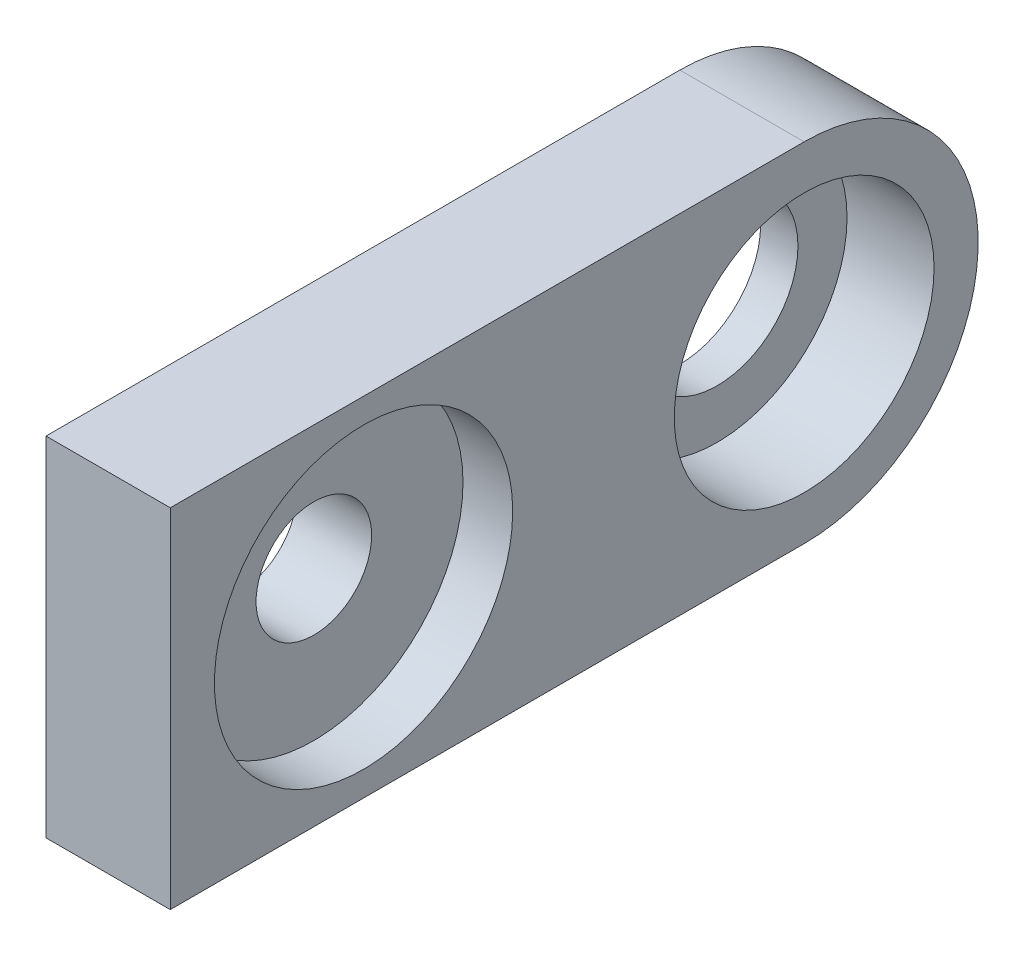
SolidWorks part; units mm, degrees
ref_plane "Front Plane" through (0, 0, 0) normal (1, 0, 0) x (0, 1, 0)
ref_plane "Top Plane" through (0, 0, 0) normal (0, 0, 1) x (0, 1, 0)
ref_plane "Right Plane" through (0, 0, 0) normal (0, 1, 0) x (-1, 0, 0)
sketch "Sketch1" plane through (0, 0, 0) normal (1, 0, 0) x (0, 1, 0)
  line L0 (-14, 0) -> (-14, 51)
  line L1 (14, 0) -> (14, 51)
  line L2 (-14, 51) -> (14, 51)
  line L3 (-14, 51) -> (14, 51) construction
  line L4 (0, 51) -> (0, -14) construction
  line L5 (-14, 0) -> (14, 0) construction
  arc A2 (-14, 0) -> (14, 0) centre (0, 0) ccw
  point P11 (0, 15.0056)
  dimension "D1" = 28
  dimension "D2" = 65
extrude "Boss-Extrude1" add sketch "Sketch1" along normal blind 10
sketch "Sketch2" plane through (10, 0, 0) normal (1, 0, 0) x (0, 1, 0)
  circle A0 centre (0, 0) radius 10.45
  dimension "D1" = 20.9
extrude "Cut-Extrude1" cut sketch "Sketch2" against normal blind 7
sketch "Sketch3" plane through (3, 0, 0) normal (1, 0, 0) x (0, 1, 0)
  circle A0 centre (0, 0) radius 6.5
  dimension "D1" = 13
extrude "Cut-Extrude2" cut sketch "Sketch3" against normal through all
sketch "Sketch4" plane through (10, 0, 0) normal (1, 0, 0) x (0, 1, 0)
  line L0 (0, 23.45) -> (0, 10.45) construction
  circle A1 centre (0, 35.45) radius 12
  circle A2 centre (0, 0) radius 10.45 construction
  dimension "D1" = 13
extrude "Cut-Extrude3" cut sketch "Sketch4" against normal blind 4
sketch "Sketch5" plane through (6, 0, 0) normal (1, 0, 0) x (0, 1, 0)
  line L0 (0, 47.45) -> (0, 23.45) construction
  circle A0 centre (0, 35.45) radius 12 construction
  circle A1 centre (0, 35.45) radius 12 construction
  circle A2 centre (0, 35.45) radius 4.65
extrude "Cut-Extrude4" cut sketch "Sketch5" against normal through all
